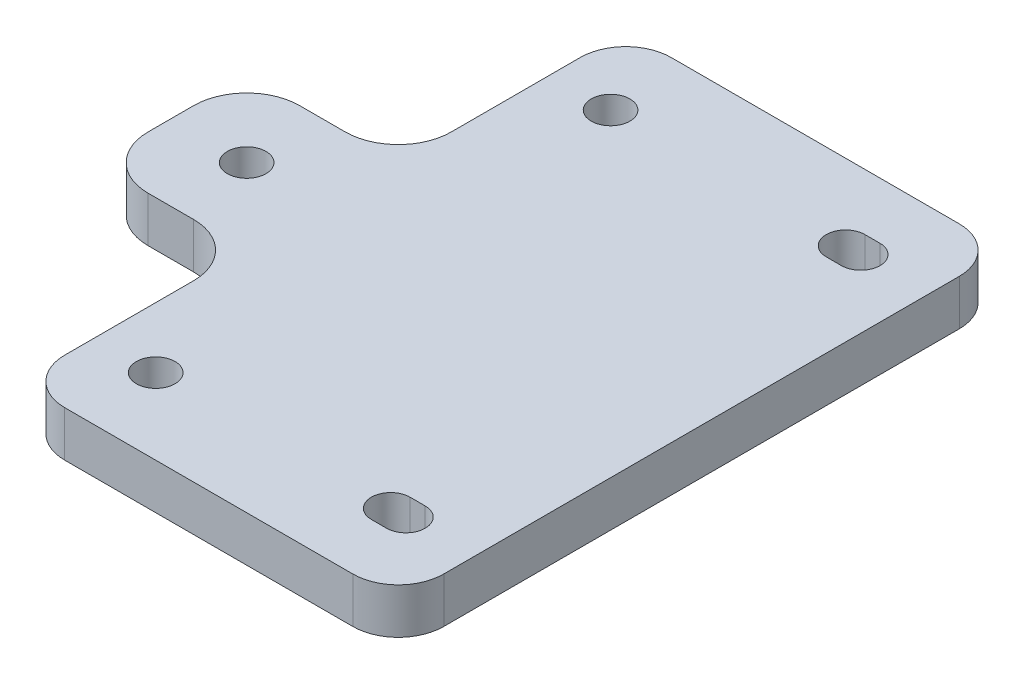
SolidWorks part; units mm, degrees
material "Клен"
ref_plane "Спереди" through (0, 0, 0) normal (0, 0, 1) x (1, 0, 0)
ref_plane "Сверху" through (0, 0, 0) normal (0, 1, 0) x (1, 0, 0)
ref_plane "Справа" through (0, 0, 0) normal (1, 0, 0) x (0, 0, -1)
sketch "Эскиз1" plane through (0, 0, 0) normal (0, 1, 0) x (1, 0, 0)
  line L0 (-56.8562, 0) -> (56.8562, 0) construction
  line L9 (-32, -10) -> (-38, -10)
  line L10 (-19, -40) -> (19, -40)
  line L11 (-25, -34) -> (-25, -17)
  line L12 (-19, 40) -> (19, 40)
  line L13 (25, -34) -> (25, 34)
  line L14 (-25, -40) -> (25, 40) construction
  line L15 (-25, 40) -> (25, -40) construction
  line L20 (-45, -3) -> (-45, 3)
  line L21 (-32, 10) -> (-38, 10)
  line L22 (-25, 17) -> (-25, 34)
  line L25 (-45, -10) -> (-25, 10) construction
  line L26 (-25, -10) -> (-72.5248, 37.5248) construction
  line L27 (-49, -29.3961) -> (-49, 34.1878) construction
  arc A4 (19, 40) -> (25, 34) centre (19, 34) cw
  arc A5 (19, -40) -> (25, -34) centre (19, -34) ccw
  arc A6 (-19, -40) -> (-25, -34) centre (-19, -34) cw
  arc A7 (-25, 34) -> (-19, 40) centre (-19, 34) cw
  circle A8 centre (-35, 0) radius 2.55
  arc A13 (-25, -17) -> (-32, -10) centre (-32, -17) ccw
  arc A14 (-32, 10) -> (-25, 17) centre (-32, 17) ccw
  arc A15 (-45, 3) -> (-38, 10) centre (-38, 3) cw
  arc A16 (-38, -10) -> (-45, -3) centre (-38, -3) cw
  point P0 (0, 0)
  point P22 (-45, -10)
  point P24 (-45, 10)
  point P25 (-75, 0)
  point P32 (-35, 0)
  point P34 (-49.8171, 0.0009)
  point P35 (-35, 0)
  point P36 (-24.7404, 0.0009)
  point P37 (-35, 0)
  point P39 (-35, 0)
  point P56 (-25, 25.5)
  dimension "D1" = 6
  dimension "D6" = 5.1
  dimension "D13" = 7
  dimension "D14" = 7
  dimension "D7" = 7
  dimension "D8" = 7
  dimension "D2" = 80
  dimension "D3" = 50
  dimension "D4" = 20
  dimension "D5" = 20
extrude "Бобышка-Вытянуть1" add sketch "Эскиз1" along normal blind 6
sketch "Эскиз2" plane through (0, 0, 0) normal (0, -1, 0) x (1, 0, 0)
  line L0 (0, -37.0349) -> (0, 29.2907) construction
  line L1 (16, -30) -> (14, -30) construction
  line L2 (16, -32.55) -> (14, -32.55)
  line L3 (16, -27.45) -> (14, -27.45)
  line L6 (-46.1924, 0) -> (55.6646, 0) construction
  line L7 (16, 30) -> (14, 30) construction
  line L8 (16, 32.55) -> (14, 32.55)
  line L9 (16, 27.45) -> (14, 27.45)
  line L10 (-25, 17) -> (-25, 34) construction
  line L11 (19, -40) -> (-19, -40) construction
  circle A0 centre (-17, -30) radius 2.55
  arc A1 (16, -32.55) -> (16, -27.45) centre (16, -30) ccw
  arc A2 (14, -27.45) -> (14, -32.55) centre (14, -30) ccw
  arc A3 (16, 32.55) -> (16, 27.45) centre (16, 30) cw
  arc A4 (14, 27.45) -> (14, 32.55) centre (14, 30) cw
  circle A5 centre (-17, 30) radius 2.55
  point P7 (15, -30)
  point P12 (15, -32.55)
  point P21 (15, 30)
  dimension "D1" = 5.1
  dimension "D2" = 5.1
  dimension "D4" = 33
  dimension "D5" = 8
  dimension "D6" = 10
extrude "Вырез-Вытянуть1" cut sketch "Эскиз2" against normal through all
equation "\"D2@Эскиз2\"=\"D1@Эскиз2\""
equation "\"D5@Эскиз1\"=\"D4@Эскиз1\""
